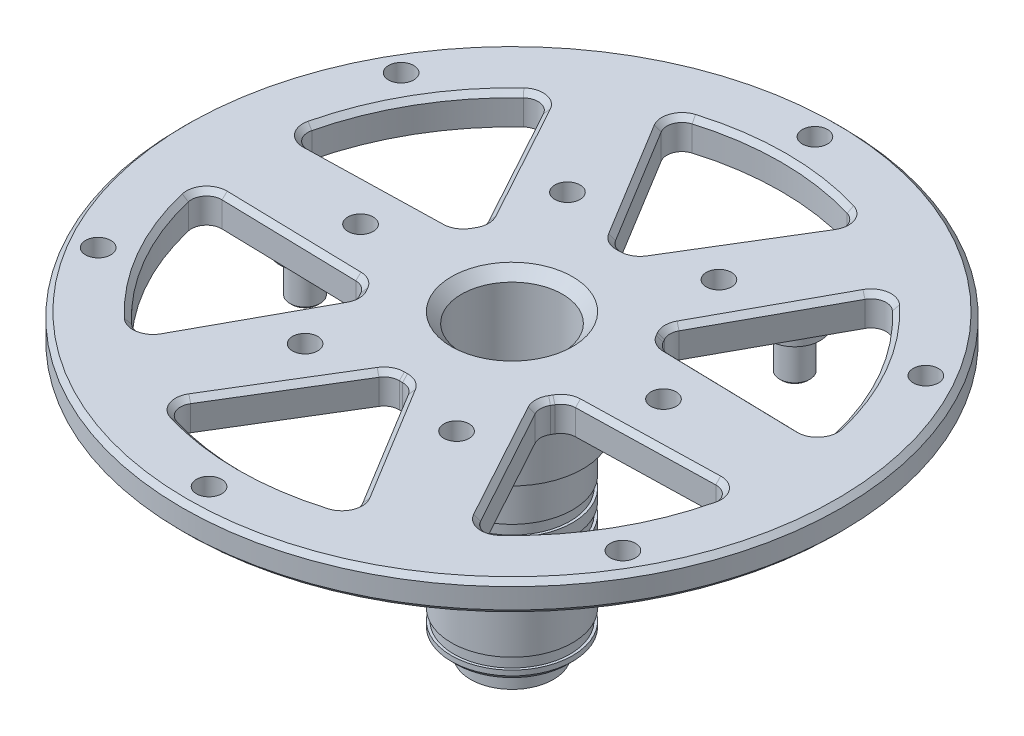
SolidWorks part; units mm, degrees
ref_plane "Front Plane" through (0, 0, 0) normal (0, 0, 1) x (1, 0, 0)
ref_plane "Top Plane" through (0, 0, 0) normal (0, 1, 0) x (1, 0, 0)
ref_plane "Right Plane" through (0, 0, 0) normal (1, 0, 0) x (0, 0, -1)
ref_axis "Axis1" through (0, 0, 0) along (0, 1, 0)
sketch "Sketch2" plane through (0, 0, 0) normal (0, 0, 1) x (1, 0, 0)
  line L0 (0, 0) -> (0, -45684.8392) construction
  line L1 (-4, 10) -> (-4, -6.5)
  line L2 (-4, -6.5) -> (-3.1, -6.5)
  line L3 (-3.1, -6.5) -> (-3.1, -9.5)
  line L4 (-3.1, -9.5) -> (-4.1, -9.5)
  line L5 (-4.1, -9.5) -> (-4.1, -7.5)
  line L6 (-4.1, -7.5) -> (-6, -7.5)
  line L7 (-6, -7.5) -> (-6, 10)
  line L9 (-11.5, -12.5) -> (11.5, -12.5) construction
  line L18 (-7, 17) -> (-7, 10)
  line L20 (-4, 10) -> (-5, 11)
  line L21 (-5, 20) -> (-32.65, 20)
  line L25 (-32.65, 17) -> (-7, 17)
  line L27 (31.65, 16) -> (-31.65, 16) construction
  line L28 (-20.098, 13.65) -> (-20.098, 18.273) construction
  line L31 (-5, 11) -> (-5, 20)
  line L37 (-7, 10) -> (-6, 10)
  line L40 (8.8, 10) -> (-8.8, 10) construction
  line L43 (-32.65, 17) -> (-32.65, 20)
  line L44 (-32.65, 15) -> (-32.65, 4) construction
  dimension "D1" = 8
  dimension "D3" = 8.2
  dimension "D4" = 12
  dimension "D5" = 2
  dimension "D6" = 1
  dimension "D7" = 1
  dimension "D8" = 2
  dimension "D9" = 5
  dimension "D10" = 1
  dimension "D12" = 3
  dimension "D13" = 1
  dimension "D15" = 20.098
  dimension "D20" = 10
  dimension "D21" = 135
revolve "Revolve1" add sketch "Sketch2" angle 360 about L0
sketch "Sketch3" plane through (0, 0, 0) normal (0, 0, 1) x (1, 0, 0)
  line L0 (-20.5, 18.273) -> (-20.5, -49187.0734) construction
  line L1 (-22, 15) -> (-23, 15)
  line L2 (-23, 15) -> (-23, 17)
  line L4 (-20.5, 17) -> (-20.5, 11)
  line L5 (-20.5, 11) -> (-22, 11)
  line L6 (-22, 15) -> (-22, 11)
  line L7 (-32.65, 17) -> (32.65, 17) construction
  line L8 (-23, 17) -> (-20.5, 17)
  line L9 (-18.8, 15) -> (-22.2, 15) construction
  dimension "D1" = 3
  dimension "D2" = 4
  dimension "D3" = 1
  dimension "D4" = 20.5
revolve "Revolve2" add sketch "Sketch3" angle 360 about L0
pattern_circular "CirPattern1" count 3 over 360 about axis through (0, 0, 0) along (0, 1, 0) of "Revolve2"
chamfer "Chamfer1" distance 0.5 angle 45 2 edges at (0, 20, 32.65) (0, 17, 32.65)
chamfer "Chamfer2" distance 1 angle 45 1 edges at (0, 20, 5)
sketch "Sketch6" plane through (0, 0, 0) normal (0, 1, 0) x (1, 0, 0)
  line L0 (0, 0) -> (39604.84, 22865.865) construction
  line L1 (26.3134, 4.2224) -> (9.9868, 4.6112)
  line L2 (8.9868, 6.3433) -> (16.8134, 20.6769)
  line L3 (0.2263, 0) -> (50000.2263, 0) construction
  arc A0 (26.3134, 4.2224) -> (16.8134, 20.6769) centre (0, 0) ccw
  arc A1 (9.9868, 4.6112) -> (8.9868, 6.3433) centre (0, 0) ccw
  circle A3 centre (0, 0) radius 32.65 construction
  circle A4 centre (0, 0) radius 7 construction
  dimension "D1" = 4
  dimension "D2" = 6
  dimension "D3" = 2
  dimension "D4" = 19
  dimension "D5" = 30
extrude "Cut-Extrude1" cut sketch "Sketch6" along normal through all
fillet "Fillet1" radius 1.5 4 edges at (26.3134, 18.5, -4.2224) (9.9868, 18.5, -4.6112) (8.9868, 18.5, -6.3433) (16.8134, 18.5, -20.6769)
hole_wizard "M3x0.5 Tapped Hole1" positions "Sketch7" profile "Sketch8" tap size "M3x0.5" standard "ANSI Metric" end condition through all
sketch "Sketch7" plane through (0, 20, 0) normal (0, 1, 0) x (1, 0, 0)
  line L0 (0, 0) -> (15, 0) construction
  line L3 (0, 0) -> (0, -9.9462) construction
  circle A0 centre (0, 0) radius 15 construction
  circle A1 centre (0, 0) radius 30 construction
  point P2 (15, 0)
  dimension "D1" = 60
  dimension "D2" = 30
  dimension "D3" = 90
sketch "Sketch8" plane through (15, 20, 0) normal (1, 0, 0) x (0, 0, 1)
  line L0 (0, 0) -> (0, 29.5)
  line L1 (0, 29.5) -> (1.25, 29.5)
  line L2 (1.25, 29.5) -> (1.25, 0)
  line L5 (1.25, 0) -> (0, 0)
  line L11 (0, -6.35) -> (0, 107.95) construction
  dimension "Thru Tap Drill Dia." = 2.5
  dimension "Thru Tap Drill Depth" = 29.5
cosmetic thread "Hole Thread3" parameters "D2"=3
pattern_circular "CirPattern2" count 6 over 360 about axis through (0, 0, 0) along (0, 1, 0) of "Cut-Extrude1", "Fillet1", "M3x0.5 Tapped Hole1"
sketch "Sketch9" plane through (0, 0, 0) normal (0, 0, 1) x (1, 0, 0)
  line L0 (0, 0) -> (0, -50000) construction
  line L1 (-8.5387, -5.4) -> (-5.75, -5.4)
  line L3 (-6.5, -6.5) -> (-5.75, -6.5)
  line L4 (-5.75, -5.4) -> (-5.75, -6.5)
  line L6 (-6.5, -6.5) -> (-5.5, -7.5)
  line L7 (-5.5, -7.5) -> (-8.5387, -7.5)
  line L8 (-8.5387, -7.5) -> (-8.5387, -5.4)
  line L9 (-6, -7.5) -> (6, -7.5) construction
  line L10 (-6, 10) -> (-6, -7.5) construction
  dimension "D1" = 11.5
  dimension "D2" = 1.1
  dimension "D3" = 45
  dimension "D4" = 1
  dimension "D5" = 0.5
revolve "Cut-Revolve1" cut sketch "Sketch9" angle 360 about L0
sketch "Sketch10" plane through (0, 0, 0) normal (0, 0, 1) x (1, 0, 0)
  line L0 (0, 0) -> (0, 50000) construction
  line L1 (-6.9577, 6) -> (-5.75, 6)
  line L2 (-6.9577, 6) -> (-6.9577, 4.9)
  line L3 (-6.9577, 4.9) -> (-5.75, 4.9)
  line L4 (-5.75, 6) -> (-5.75, 4.9)
  line L5 (-9, 6) -> (9, 6) construction
  dimension "D1" = 11.5
  dimension "D2" = 1.1
revolve "Cut-Revolve2" cut sketch "Sketch10" angle 360 about L0
sketch "Sketch11" plane through (0, 0, 0) normal (0, 0, 1) x (1, 0, 0)
  line L0 (0, 0) -> (0, -50000) construction
  line L1 (-8.902, 3.7) -> (-5.75, 3.7)
  line L2 (-8.902, 3.7) -> (-8.902, 2.6)
  line L3 (-8.902, 2.6) -> (-5.75, 2.6)
  line L4 (-5.75, 3.7) -> (-5.75, 2.6)
  line L7 (8.8, 2.6) -> (-8.8, 2.6) construction
  dimension "D1" = 11.5
  dimension "D2" = 1.1
revolve "Cut-Revolve3" cut sketch "Sketch11" angle 360 about L0
hole_wizard "M3x0.5 Tapped Hole2" positions "Sketch12" profile "Sketch13" tap size "M3x0.5" standard "ANSI Metric" end condition through all
sketch "Sketch12" plane through (0, 20, 0) normal (0, 1, 0) x (1, 0, 0)
  circle A0 centre (0, 0) radius 30 construction
  point P0 (0, 30)
  dimension "D1" = 60
sketch "Sketch13" plane through (0, 20, -30) normal (1, 0, 0) x (0, 0, 1)
  line L0 (0, 0) -> (0, 29.5)
  line L1 (0, 29.5) -> (1.25, 29.5)
  line L2 (1.25, 29.5) -> (1.25, 0)
  line L5 (1.25, 0) -> (0, 0)
  line L11 (0, -6.35) -> (0, 107.95) construction
  dimension "Thru Tap Drill Dia." = 2.5
  dimension "Thru Tap Drill Depth" = 29.5
cosmetic thread "Hole Thread4" parameters "D2"=3
pattern_circular "CirPattern3" count 6 over 360 about axis through (0, 0, 0) along (0, 1, 0) of "M3x0.5 Tapped Hole2"
chamfer "Chamfer3" distance 0.5 angle 45 48 edges at (-9.5263, 20, -5.5) (-9.2321, 20, -6.3802) (-10.1415, 20, -4.8052) (-12.6664, 20, -13.082) (-17.6625, 20, -4.4284) (-16.9978, 20, -19.7984) (-25.6448, 20, -4.8214) (-23.0796, 20, -13.325) (9.5263, 20, -5.5) (10.1415, 20, -4.8052) (9.2321, 20, -6.3802) (17.6625, 20, -4.4284) (12.6664, 20, -13.082) (25.6448, 20, -4.8214) (16.9978, 20, -19.7984) (23.0796, 20, -13.325) (0, 20, -11) (0.9094, 20, -11.1854) (-0.9094, 20, -11.1854) (4.9961, 20, -17.5104) (-4.9961, 20, -17.5104) (8.647, 20, -24.6198) (-8.647, 20, -24.6198) (0, 20, -26.65) (-17.6625, 20, 4.4284) (-25.6448, 20, 4.8214) (-10.1415, 20, 4.8052) (-23.0796, 20, 13.325) (-9.5263, 20, 5.5) (-16.9978, 20, 19.7984) (-9.2321, 20, 6.3802) (-12.6664, 20, 13.082) (-4.9961, 20, 17.5104) (-8.647, 20, 24.6198) (-0.9094, 20, 11.1854) (0, 20, 26.65) (0, 20, 11) (8.647, 20, 24.6198) (0.9094, 20, 11.1854) (4.9961, 20, 17.5104) (17.6625, 20, 4.4284) (10.1415, 20, 4.8052) (25.6448, 20, 4.8214) (9.5263, 20, 5.5) (23.0796, 20, 13.325) (9.2321, 20, 6.3802) (16.9978, 20, 19.7984) (12.6664, 20, 13.082)
chamfer "Chamfer4" distance 0.2 angle 45 3 edges at (11, 11, -19.0526) (11, 11, 19.0526) (-22, 11, 0)
